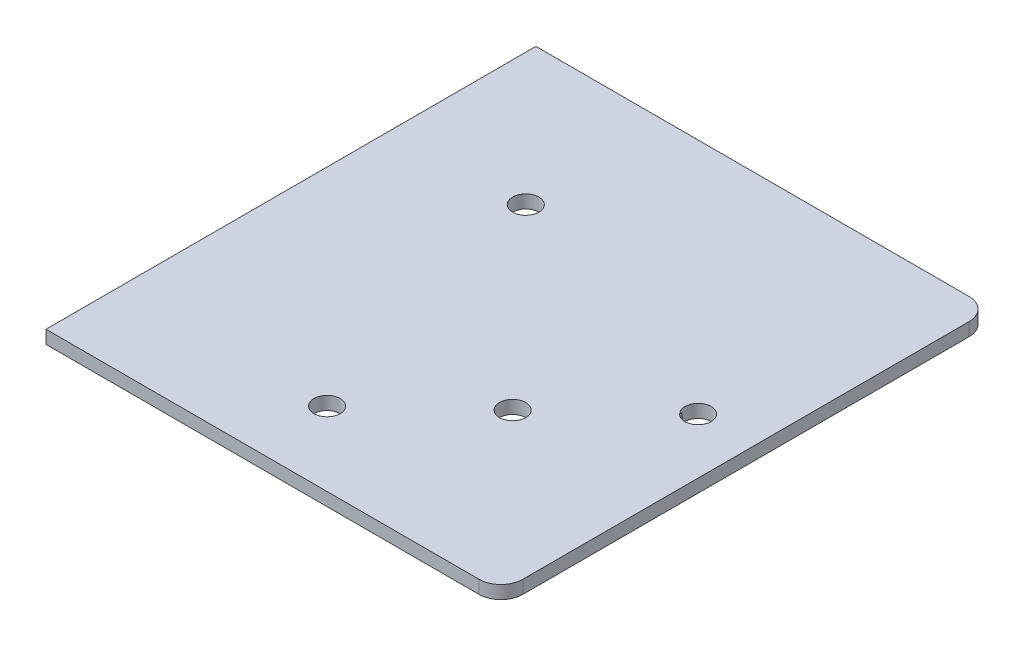
SolidWorks part; units mm, degrees
material "Oak"
ref_plane "Front Plane" through (0, 0, 0) normal (0, 0, 1) x (1, 0, 0)
ref_plane "Top Plane" through (0, 0, 0) normal (0, 1, 0) x (1, 0, 0)
ref_plane "Right Plane" through (0, 0, 0) normal (1, 0, 0) x (0, 0, -1)
sketch "Sketch1" plane through (0, 0, 0) normal (0, 1, 0) x (1, 0, 0)
  line L0 (558.8, 99.2707) -> (461.5124, 17.6367)
  line L1 (-558.8, -177.8) -> (558.8, -177.8)
  line L2 (-558.8, 177.8) -> (558.8, 177.8)
  line L3 (558.8, -177.8) -> (558.8, 177.8)
  line L4 (-558.8, -177.8) -> (558.8, 177.8) construction
  line L5 (-558.8, 177.8) -> (558.8, -177.8) construction
  line L6 (-228.6, 177.8) -> (228.6, 177.8)
  line L7 (-228.6, -177.8) -> (228.6, -177.8)
  line L8 (228.6, 177.8) -> (228.6, -177.8)
  line L9 (-228.6, 177.8) -> (228.6, -177.8) construction
  line L10 (-228.6, -177.8) -> (228.6, 177.8) construction
  line L11 (228.6, -177.8) -> (558.8, 99.2707)
  line L12 (-228.6, 177.8) -> (-228.6, -177.8)
  point P4 (0, 0)
extrude "Boss-Extrude1" add sketch "Sketch1" along normal blind 9.525 contours L8 L11 L0 L3 L2 region at (358.5765, 0, -54.5316)
extrude "Boss-Extrude2" add sketch "Sketch1<4>" along normal blind 9.525 contours L11 L1 L3 L0 region at (448.7333, 0, 85.4431)
sketch "Sketch1<4>" plane through (0, 0, 0) normal (0, 1, 0) x (1, 0, 0) same geometry as "Sketch1"
sketch "Sketch3" plane through (0, 0, 0) normal (0, -1, 0) x (1, 0, 0)
  line L0 (558.8, 177.8) -> (228.6, -177.8)
  line L1 (228.6, 177.8) -> (558.8, -177.8)
  line L2 (228.6, -177.8) -> (393.7, -177.8)
  line L3 (228.6, -177.8) -> (558.8, -177.8) construction
  line L4 (393.7, 0) -> (324.3762, -74.6564)
  line L5 (393.7, 0) -> (228.6, 0)
  line L6 (228.6, -177.8) -> (228.6, 177.8) construction
  line L7 (393.7, 0) -> (558.8, 0)
  line L8 (228.6, 0) -> (228.6, 177.8)
  line L9 (558.8, 177.8) -> (558.8, -177.8) construction
  line L10 (448.729, 59.262) -> (378.9304, 124.075)
  line L11 (448.729, 59.262) -> (518.5276, -5.551)
  line L16 (228.6, 177.8) -> (228.6, -177.8)
  line L17 (228.6, -177.8) -> (558.8, -177.8)
  line L20 (558.8, -177.8) -> (558.8, 177.8)
  line L21 (558.8, 177.8) -> (228.6, 177.8)
  line L22 (228.6, 177.8) -> (228.6, -177.8)
  line L23 (228.6, -177.8) -> (558.8, -177.8)
  line L24 (558.8, -177.8) -> (558.8, 177.8)
  line L26 (558.8, 177.8) -> (228.6, 177.8)
  circle A0 centre (324.3762, -74.6564) radius 9.525
  circle A1 centre (448.729, 59.262) radius 9.525
  circle A2 centre (378.9304, 124.075) radius 9.525
  circle A3 centre (518.5276, -5.551) radius 9.525
  dimension "D1" = 101.6
  dimension "D6" = 0
fillet "Fillet1" radius 15.875 2 edges at (558.8, 4.7625, 177.8) (558.8, 4.7625, -177.8)
extrude "Cut-Extrude1" cut sketch "Sketch3" against normal through all contours A2 | L11 A1 L0 | L0 A1 L11 | L10 A1 L0 | L7 A3 | L7 A3 L11 | L0 A1 L10 | L0 A0 L4 | L4 A0 L0 region at (370.3153, 0, 127.4581) region at (454.4421, 0, 59.4736) region at (448.5174, 0, 64.9751) region at (448.9406, 0, 53.5489) region at (443.0159, 0, 59.0504) region at (518.5276, 0, -6.8289) region at (518.6641, 0, 1.6478) region at (327.3386, 0, -77.4071) region at (321.4139, 0, -71.9056)
